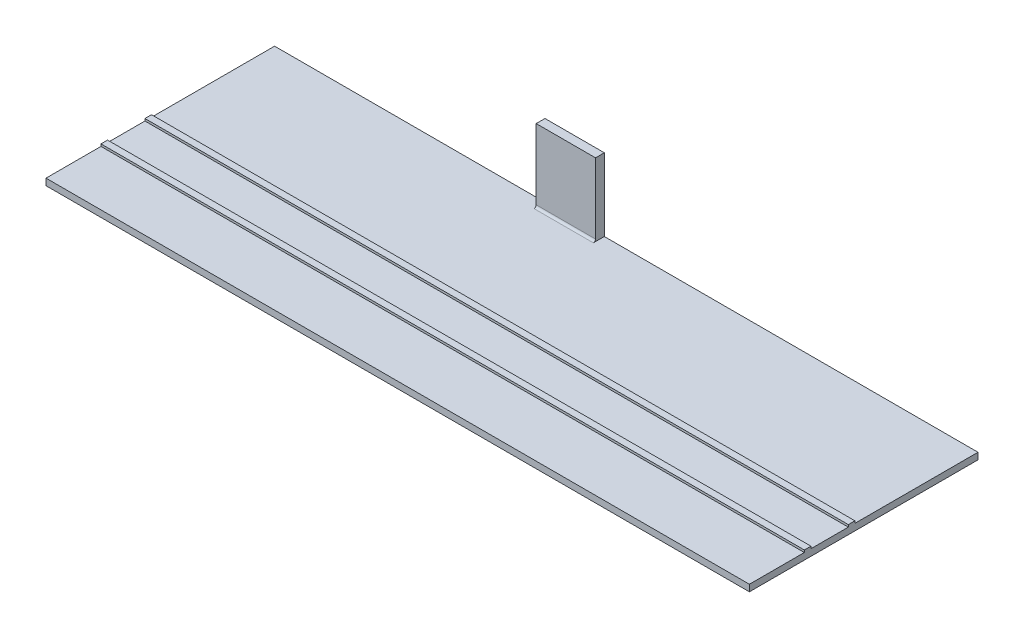
SolidWorks part; units mm, degrees
ref_plane "Piano frontale" through (0, 0, 0) normal (0, 0, 1) x (1, 0, 0)
ref_plane "Piano superiore" through (0, 0, 0) normal (0, 1, 0) x (1, 0, 0)
ref_plane "Piano destro" through (0, 0, 0) normal (1, 0, 0) x (0, 0, -1)
sketch "Schizzo1" plane through (0, 0, 0) normal (0, 0, 1) x (1, 0, 0)
  line L1 (0, 0) -> (27, 0)
  line L2 (0, 0) -> (0, -36)
  line L3 (0, -36) -> (27, -36)
  line L4 (27, 0) -> (27, -36)
  dimension "D1" = 27
  dimension "D2" = 36
extrude "Estrusione-Estrusione1" add sketch "Schizzo1" along normal blind 4
sketch "Schizzo3" plane through (0, 0, 4) normal (0, 0, 1) x (1, 0, 0)
  line L0 (27, -36) -> (27, 0) construction
  line L1 (0, -36) -> (27, -36)
  line L2 (0, -36) -> (0, -33)
  line L3 (0, -33) -> (27, -33)
  line L4 (27, -36) -> (27, -33)
  dimension "D1" = 3
extrude "Estrusione-Estrusione2" add sketch "Schizzo3" along normal blind 100
fillet "Raccordo1" radius 1 1 edges at (13.5, -33, 4)
sketch "Schizzo5" plane through (27, 0, 0) normal (1, 0, 0) x (0, 0, -1)
  line L0 (0, -36) -> (0, 0) construction
  line L1 (-104, -36) -> (0, -36)
  line L2 (-104, -36) -> (-104, -33)
  line L3 (-104, -33) -> (0, -33)
  line L4 (0, -36) -> (0, -33)
  line L9 (-104, -33) -> (-5, -33) construction
extrude "Estrusione-Estrusione3" add sketch "Schizzo5" along normal blind 170 and the other way blind 150
sketch "Schizzo6" plane through (-123, 0, 0) normal (-1, 0, 0) x (0, 0, 1)
  line L0 (56, -33) -> (56, -32.5)
  line L1 (0, -33) -> (104, -33) construction
  line L3 (56, -32.5) -> (56, -32)
  line L4 (56, -32) -> (59, -32)
  line L5 (59, -32) -> (59, -32.5)
  line L6 (76, -33) -> (79, -33)
  line L7 (59, -32.5) -> (59, -33)
  line L8 (76, -33) -> (76, -32)
  line L9 (76, -32) -> (79, -32)
  line L10 (79, -33) -> (79, -32)
  line M11 (104, -33) -> (0, -33)
  dimension "D1" = 1
  dimension "D2" = 3
  dimension "D3" = 3
  dimension "D4" = 1
  dimension "D5" = 17
  dimension "D6" = 25
extrude "Estrusione-Estrusione4" add sketch "Schizzo6" against normal blind 320 contours L7 L5 L4 L3 L0 M11 | L10 L9 L8 M11 region at (-123, -32.5, 77.5) region at (-123, -32.5, 57.5)
